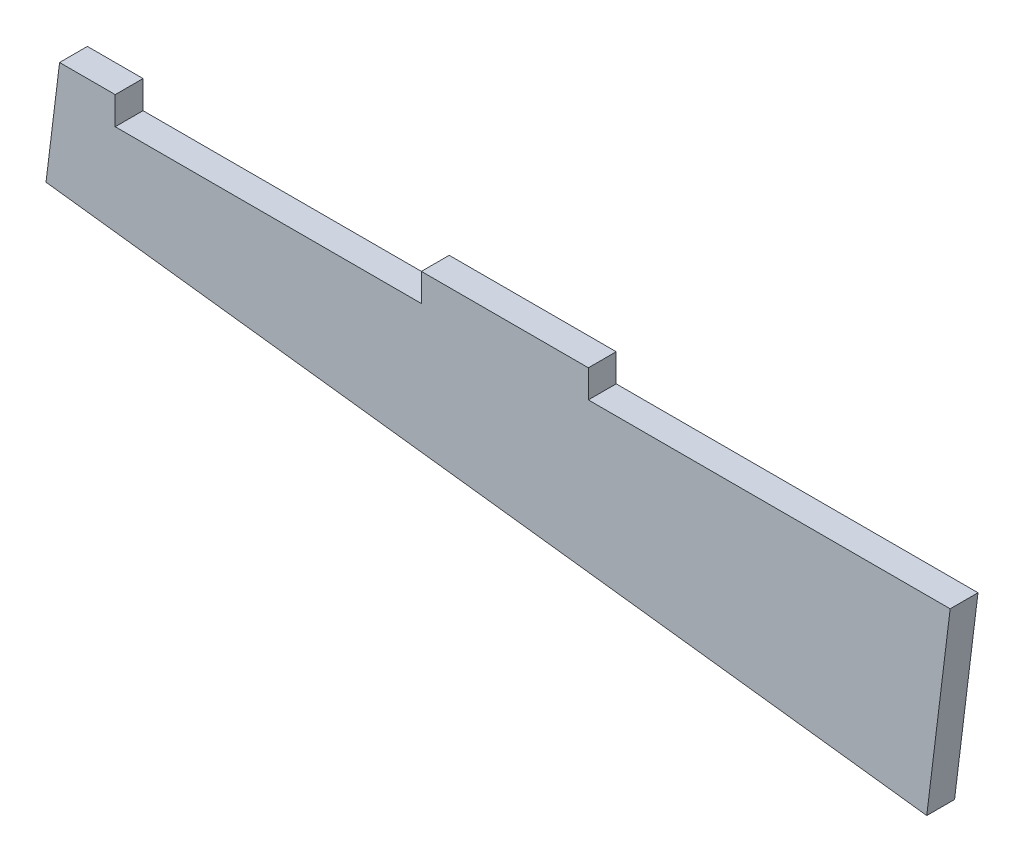
SolidWorks part; units mm, degrees
ref_plane "Front Plane" through (0, 0, 0) normal (0, 0, 1) x (1, 0, 0)
ref_plane "Top Plane" through (0, 0, 0) normal (0, 1, 0) x (1, 0, 0)
ref_plane "Right Plane" through (0, 0, 0) normal (1, 0, 0) x (0, 0, -1)
sketch "Sketch1" plane through (0, 0, 0) normal (0, 0, 1) x (1, 0, 0)
  line L0 (-195.3168, -62.6592) -> (-182.6168, -62.6592)
  line L4 (-182.6168, -62.6592) -> (-182.6168, -69.0092)
  line L5 (-182.6168, -69.0092) -> (-112.7668, -69.0092)
  line L6 (-112.7668, -69.0092) -> (-112.7668, -62.6592)
  line L7 (-112.7668, -62.6592) -> (-74.6668, -62.6592)
  line L8 (-74.6668, -62.6592) -> (-74.6668, -69.0092)
  line L9 (-74.6668, -69.0092) -> (7.8832, -69.0092)
  line L10 (7.8832, -69.0092) -> (2.5379, -112.5435)
  line L11 (2.5379, -112.5435) -> (-198.4122, -87.8699)
  line L12 (-198.4122, -87.8699) -> (-195.3168, -62.6592)
  line L13 (-412.7613, -14.2454) -> (-31.7613, -61.0264) construction
  dimension "D1" = 12.7
  dimension "D2" = 6.35
  dimension "D3" = 69.85
  dimension "D4" = 38.1
  dimension "D5" = 82.55
  dimension "D6" = 25.4
extrude "Boss-Extrude1" add sketch "Sketch1" against normal blind 6.35
